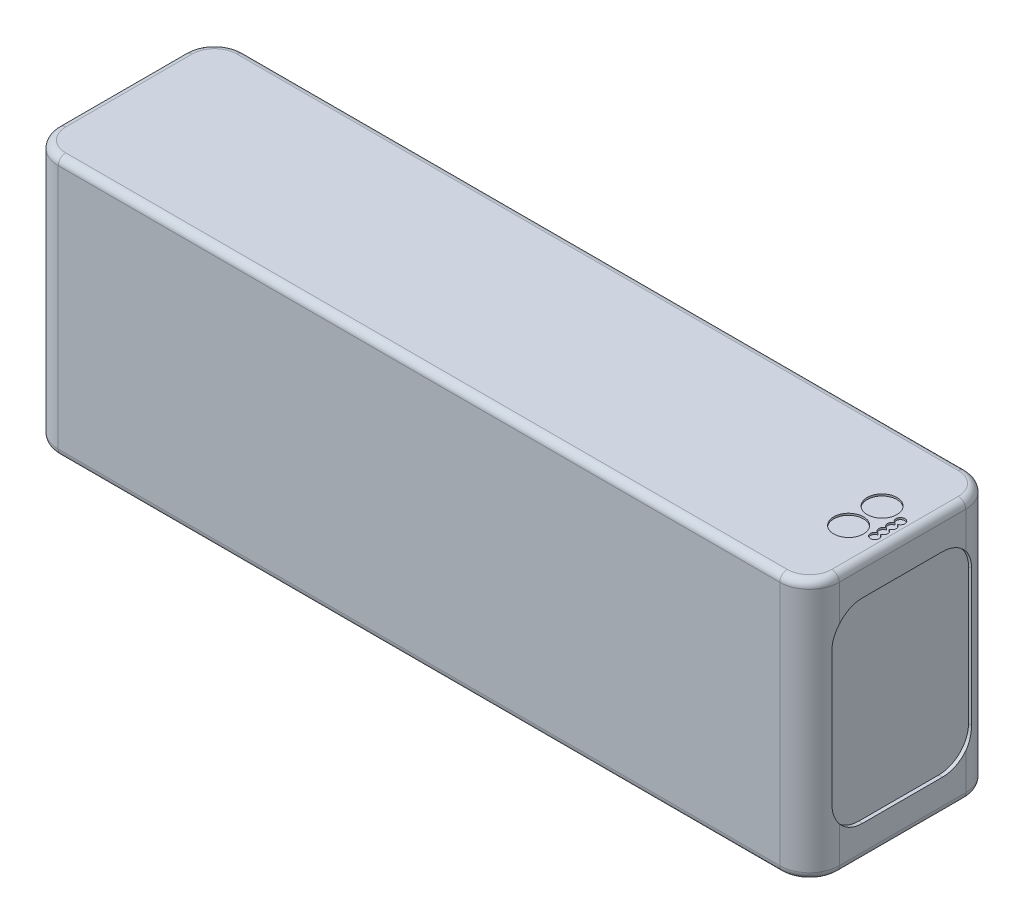
SolidWorks part; units mm, degrees
ref_plane "Front Plane" through (0, 0, 0) normal (0, 0, 1) x (1, 0, 0)
ref_plane "Top Plane" through (0, 0, 0) normal (0, 1, 0) x (1, 0, 0)
ref_plane "Right Plane" through (0, 0, 0) normal (1, 0, 0) x (0, 0, -1)
ref_plane "Plane1" through (0, 0, -15) normal (0, 0, -1) x (-1, 0, 0)
sketch "Sketch1" plane through (0, 0, -15) normal (0, 0, -1) x (-1, 0, 0)
  line L0 (-52.5, -17.5) -> (52.5, -17.5)
  line L1 (52.5, -17.5) -> (52.5, 17.5)
  line L2 (52.5, 17.5) -> (-52.5, 17.5)
  line L3 (-52.5, 17.5) -> (-52.5, -17.5)
  line L4 (-52.5, 0) -> (52.5, 0) construction
  line L5 (0, 17.5) -> (0, -17.5) construction
  dimension "D1" = 35
  dimension "D2" = 105
extrude "Boss-Extrude1" add sketch "Sketch1" against normal blind 25
sketch "Sketch2" plane through (52.5, 0, 0) normal (1, 0, 0) x (0, 0, -1)
  line L0 (-6.875, 9.125) -> (-6.875, -9.125)
  line L1 (-2.875, -13.125) -> (7.875, -13.125)
  line L2 (11.875, -9.125) -> (11.875, 9.125)
  line L3 (7.875, 13.125) -> (-2.875, 13.125)
  line L4 (-10, 17.5) -> (15, -17.5) construction
  line L5 (15, 17.5) -> (-10, -17.5) construction
  line L6 (-6.875, 13.125) -> (11.875, -13.125) construction
  line L7 (11.875, 13.125) -> (-6.875, -13.125) construction
  line L12 (-10, 17.5) -> (15, 17.5) construction
  line L13 (-10, 17.5) -> (-10, -17.5) construction
  line L14 (-10, -17.5) -> (15, -17.5) construction
  line L15 (15, 17.5) -> (15, -17.5) construction
  line L16 (-10, 17.5) -> (15, -17.5) construction
  line L17 (-10, -17.5) -> (15, 17.5) construction
  arc A0 (-6.875, -9.125) -> (-2.875, -13.125) centre (-2.875, -9.125) ccw
  arc A1 (7.875, -13.125) -> (11.875, -9.125) centre (7.875, -9.125) ccw
  arc A2 (11.875, 9.125) -> (7.875, 13.125) centre (7.875, 9.125) ccw
  arc A3 (-6.875, 9.125) -> (-2.875, 13.125) centre (-2.875, 9.125) cw
  point P16 (2.5, 0)
  dimension "D3" = 4
  dimension "D1" = 18.75
  dimension "D2" = 25
extrude "Cut-Extrude1" cut sketch "Sketch2" against normal blind 0.5
sketch "Sketch3" plane through (-52.5, 0, 0) normal (-1, 0, 0) x (0, 0, 1)
  line L0 (2.875, 13.125) -> (-7.875, 13.125)
  line L1 (-11.875, 9.125) -> (-11.875, -9.125)
  line L2 (-7.875, -13.125) -> (2.875, -13.125)
  line L3 (6.875, -9.125) -> (6.875, 9.125)
  line L4 (-11.875, 13.125) -> (6.875, -13.125) construction
  line L5 (6.875, 13.125) -> (-11.875, -13.125) construction
  line L6 (-15, 17.5) -> (10, -17.5) construction
  line L7 (10, -17.5) -> (-15, -17.5) construction
  line L8 (-15, -17.5) -> (10, 17.5) construction
  arc A0 (-11.875, -9.125) -> (-7.875, -13.125) centre (-7.875, -9.125) ccw
  arc A1 (2.875, -13.125) -> (6.875, -9.125) centre (2.875, -9.125) ccw
  arc A2 (2.875, 13.125) -> (6.875, 9.125) centre (2.875, 9.125) cw
  arc A3 (-7.875, 13.125) -> (-11.875, 9.125) centre (-7.875, 9.125) ccw
  dimension "D3" = 4
  dimension "D1" = 18.75
  dimension "D2" = 25
extrude "Cut-Extrude2" cut sketch "Sketch3" against normal blind 0.5
fillet "Fillet1" radius 4 4 edges at (-52.5, 0, -15) (-52.5, 0, 10) (52.5, 0, -15) (52.5, 0, 10) tangent propagation no
fillet "Fillet2" radius 1 16 edges at (51.3284, 17.5, -13.8284) (52.5, 17.5, -2.5) (0, 17.5, -15) (51.3284, 17.5, 8.8284) (-51.3284, 17.5, -13.8284) (0, 17.5, 10) (-52.5, 17.5, -2.5) (-51.3284, 17.5, 8.8284) (-52.5, -17.5, -2.5) (-51.3284, -17.5, -13.8284) (-51.3284, -17.5, 8.8284) (0, -17.5, -15) (0, -17.5, 10) (51.3284, -17.5, -13.8284) (51.3284, -17.5, 8.8284) (52.5, -17.5, -2.5) tangent propagation no
sketch "Sketch4" plane through (0, 0, 10) normal (0, 0, 1) x (1, 0, 0)
  line L0 (-48.5, 0) -> (48.5, 0) construction
  line L1 (-48.5, 16.5) -> (-48.5, -16.5) construction
  line L2 (48.5, -16.5) -> (48.5, 16.5) construction
  line L3 (0, 25.9735) -> (0, -16.5) construction
  line L4 (-48.5, -16.5) -> (48.5, -16.5) construction
  circle A0 centre (0, 0) radius 0.5026
sketch "Sketch5" plane through (0, 17.5, 0) normal (0, 1, 0) x (1, 0, 0)
  line L0 (47.5, -2.5068) -> (47.5, 11.9202) construction
  line L1 (51.5, 2.5) -> (37.3937, 2.5) construction
  line L2 (51.5, -6) -> (51.5, 11) construction
  line L4 (48.5, -10) -> (-48.5, -10) construction
  line L5 (52.5, 11) -> (52.5, -6) construction
  circle A0 centre (47.5, 0.25) radius 2
  circle A1 centre (47.5, 4.75) radius 2
  dimension "D1" = 4
  dimension "D2" = 4
  dimension "D3" = 4.5
  dimension "D4" = 12.5
  dimension "D5" = 2.25
  dimension "D6" = 5
extrude "Cut-Extrude3" cut sketch "Sketch5" against normal blind 0.25 contours A0 | A1
sketch "Sketch6" plane through (0, 17.5, 0) normal (0, 1, 0) x (1, 0, 0)
  line L0 (40.4856, 2.5) -> (50.5, 2.5) construction
  line L1 (-48.5, 15) -> (48.5, 15) construction
  line L2 (50.5, 8.3849) -> (50.5, -5.8297) construction
  line L3 (52.5, 11) -> (52.5, -6) construction
  arc A0 (50.6714, 3.65) -> (50.3286, 3.65) centre (50.5, 4.225) ccw
  arc A1 (50.3286, 3.65) -> (50.3286, 2.5) centre (50.5, 3.075) ccw
  arc A2 (50.3286, 2.5) -> (50.3286, 1.35) centre (50.5, 1.925) ccw
  arc A3 (50.3286, 1.35) -> (50.6714, 1.35) centre (50.5, 0.775) ccw
  arc A4 (50.6714, 2.5) -> (50.6714, 3.65) centre (50.5, 3.075) ccw
  arc A5 (50.6714, 1.35) -> (50.6714, 2.5) centre (50.5, 1.925) ccw
  dimension "D3" = 1.2
  dimension "D4" = 1.15
  dimension "D5" = 1.15
  dimension "D6" = 1.15
  dimension "D7" = 0.575
  dimension "D1" = 12.5
  dimension "D2" = 2
extrude "Cut-Extrude4" cut sketch "Sketch6" against normal blind 0.25
sketch "Sketch7" plane through (0, 17.5, 0) normal (0, 1, 0) x (1, 0, 0)
  point P0 (47.5, 4.75)
  point P1 (47.5, 0.25)
  point P3 (50.5, 3.075)
  point P5 (50.5, 1.925)
  point P7 (50.5, 0.775)
  point P9 (50.5, 4.225)
other "CPoint1" parameters "Diameter"=3, "StubLength"=2
ref_axis "Axis1" through (47.5, 27.5, -0.25) along (0, -1, 0)
other "CPoint2" parameters "Diameter"=3, "StubLength"=2
ref_axis "Axis2" through (47.5, 27.5, -4.75) along (0, -1, 0)
equation "\"D1@Sketch3\"=\"D2@Sketch3\" * .75"
equation "\"D1@Sketch2\"=\"D2@Sketch2\"* .75"
